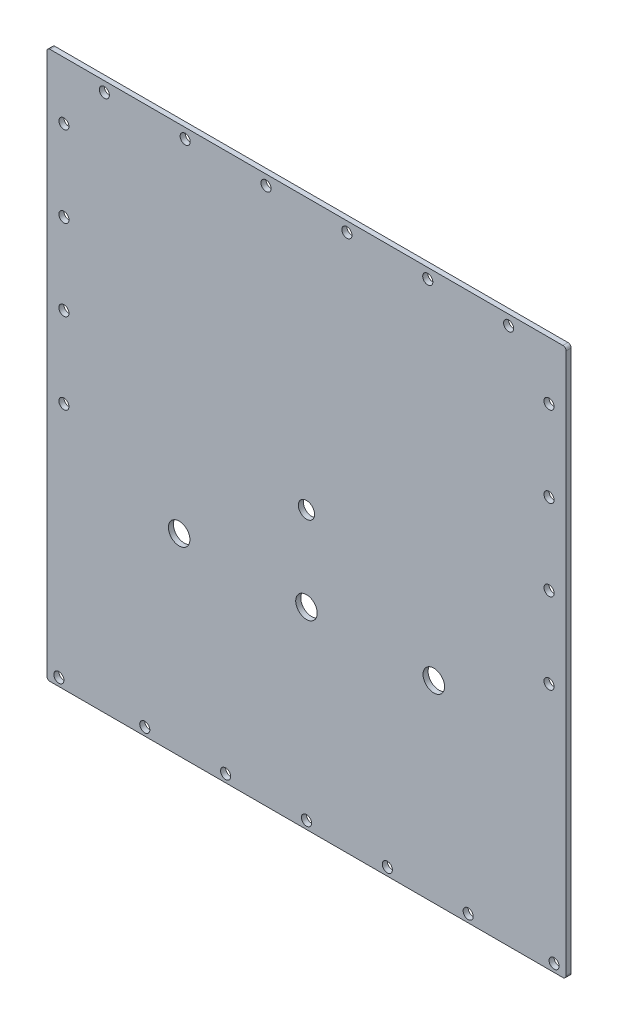
SolidWorks part; units mm, degrees
material "6061 Alloy"
ref_plane "Front Plane" through (0, 0, 0) normal (0, 0, 1) x (1, 0, 0)
ref_plane "Top Plane" through (0, 0, 0) normal (0, 1, 0) x (1, 0, 0)
ref_plane "Right Plane" through (0, 0, 0) normal (1, 0, 0) x (0, 0, -1)
sketch "Sketch2" plane through (0, 0, 0) normal (0, 0, 1) x (1, 0, 0)
  line L0 (0, -176.7623) -> (165.1, -176.7623)
  line L1 (0, 0) -> (165.1, 0)
  line L5 (82.55, 0) -> (82.55, -176.7623) construction
  line L6 (165.1, 0) -> (165.1, -176.7623)
  line L7 (0, 0) -> (0, -176.7623)
  line L8 (0, 0) -> (0, -176.7623)
  line L9 (0, -171.98) -> (165.1, -171.98)
  line L10 (1, 0) -> (1, -171.98)
  line L11 (164.1, -171.98) -> (164.1, 0)
  circle A31 centre (31.75, -169.48) radius 1.5875
  circle A32 centre (57.15, -169.48) radius 1.5875
  circle A33 centre (82.55, -169.48) radius 1.5875
  circle A34 centre (107.95, -169.48) radius 1.5875
  circle A35 centre (133.35, -169.48) radius 1.5875
  circle A63 centre (6.35, -18.05) radius 1.5875
  circle A65 centre (160.3375, -169.48) radius 1.5875
  circle A66 centre (4.7625, -169.48) radius 1.5875
  circle A67 centre (82.55, -85) radius 2.5527
  circle A69 centre (19.05, -3.175) radius 1.5875
  circle A70 centre (44.45, -3.175) radius 1.5875
  circle A71 centre (69.85, -3.175) radius 1.5875
  circle A72 centre (95.25, -3.175) radius 1.5875
  circle A73 centre (120.65, -3.175) radius 1.5875
  circle A74 centre (146.05, -3.175) radius 1.5875
  circle A76 centre (6.35, -43.45) radius 1.5875
  circle A77 centre (6.35, -68.85) radius 1.5875
  circle A78 centre (6.35, -94.25) radius 1.5875
  circle A81 centre (158.75, -68.85) radius 1.5875
  circle A82 centre (158.75, -94.25) radius 1.5875
  circle A83 centre (158.75, -43.45) radius 1.5875
  circle A84 centre (158.75, -18.05) radius 1.5875
  dimension "D9" = 3.175
  dimension "D4" = 3.175
  dimension "D21" = 5.1054
  dimension "D1" = 165.1
  dimension "D23" = 25.4
  dimension "D5" = 176.7623
  dimension "D8" = 31.75
  dimension "D11" = 7.2823
  dimension "D10" = 19.05
  dimension "D12" = 3.175
  dimension "D14" = 25.4
  dimension "D3" = 18.05
  dimension "D6" = 6.35
  dimension "D15" = 25.4
  dimension "D16" = 2.5
  dimension "D17" = 4.7625
  dimension "D18" = 1
  dimension "D19" = 1
  dimension "D20" = 85
  dimension "D22" = 5
  dimension "D13" = 3
  dimension "D7" = 4
extrude "Boss-Extrude2" add sketch "Sketch2" along normal blind 1.5875 contours L1 L0 A35 A34 A33 A32 A31 | L1 L5 A33 L0 L6 A35 A34 region at (3.3702, -85.99, 0)
fillet "Fillet1" radius 1 4 edges at (1, -171.98, 0.7937) (1, 0, 0.7937) (164.1, 0, 0.7937) (164.1, -171.98, 0.7937)
sketch "Sketch3" plane through (0, 0, 1.5875) normal (0, 0, 1) x (1, 0, 0)
  line L0 (2, -171.98) -> (163.1, -171.98) construction
  line L2 (1, -1) -> (1, -170.98) construction
  circle A0 centre (42.55, -111.451) radius 3.38
  circle A1 centre (82.55, -111.451) radius 3.38
  circle A2 centre (122.55, -111.451) radius 3.38
  point P8 (0, 0)
  dimension "D4" = 6.76
  dimension "D1" = 40
  dimension "D2" = 40
  dimension "D3" = 60.529
  dimension "D5" = 41.55
extrude "Cut-Extrude1" cut sketch "Sketch3" against normal through all both and the other way through all
equation "\"D19@Sketch2\"=\"D18@Sketch2\""
equation "\"D9@Sketch2\"=\"D4@Sketch2\""
